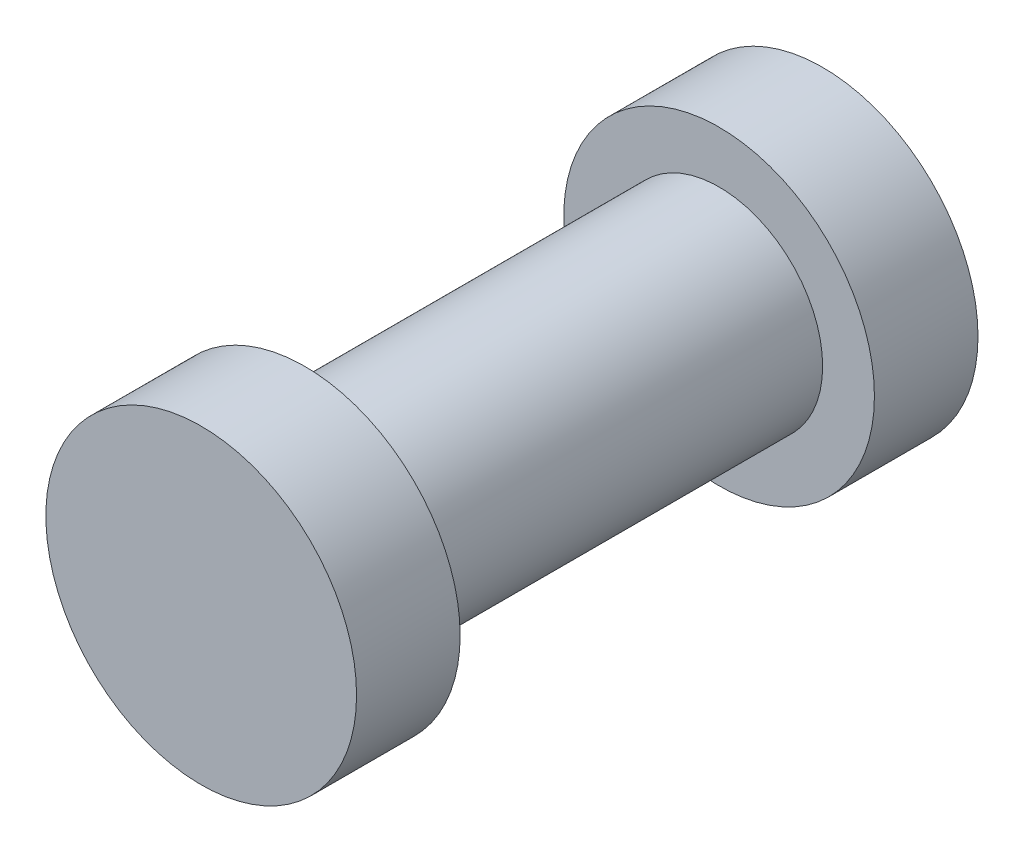
SolidWorks part; units mm, degrees
ref_plane "Front Plane" through (0, 0, 0) normal (0, 0, 1) x (1, 0, 0)
ref_plane "Top Plane" through (0, 0, 0) normal (0, 1, 0) x (1, 0, 0)
ref_plane "Right Plane" through (0, 0, 0) normal (1, 0, 0) x (0, 0, -1)
sketch "Sketch1" plane through (0, 0, 0) normal (0, 0, 1) x (1, 0, 0)
  circle A0 centre (0, 0) radius 5
  circle A1 centre (0, 0) radius 7.5
  dimension "D1" = 10
  dimension "D2" = 15
extrude "Boss-Extrude1" add sketch "Sketch1" along normal blind 30 contours A0 | A1 A0 region at (0, 0, 0) region at (-7.2879, 0, 0)
extrude "Cut-Extrude1" cut sketch "Sketch1<6>" along normal offset from surface (20 mm away) 5 from offset 5 contours A1 A0 region at (-7.2879, 0, 0) up to face at (7.5, 0, 30)
sketch "Sketch1<6>" plane through (0, 0, 0) normal (0, 0, 1) x (1, 0, 0) same geometry as "Sketch1"
